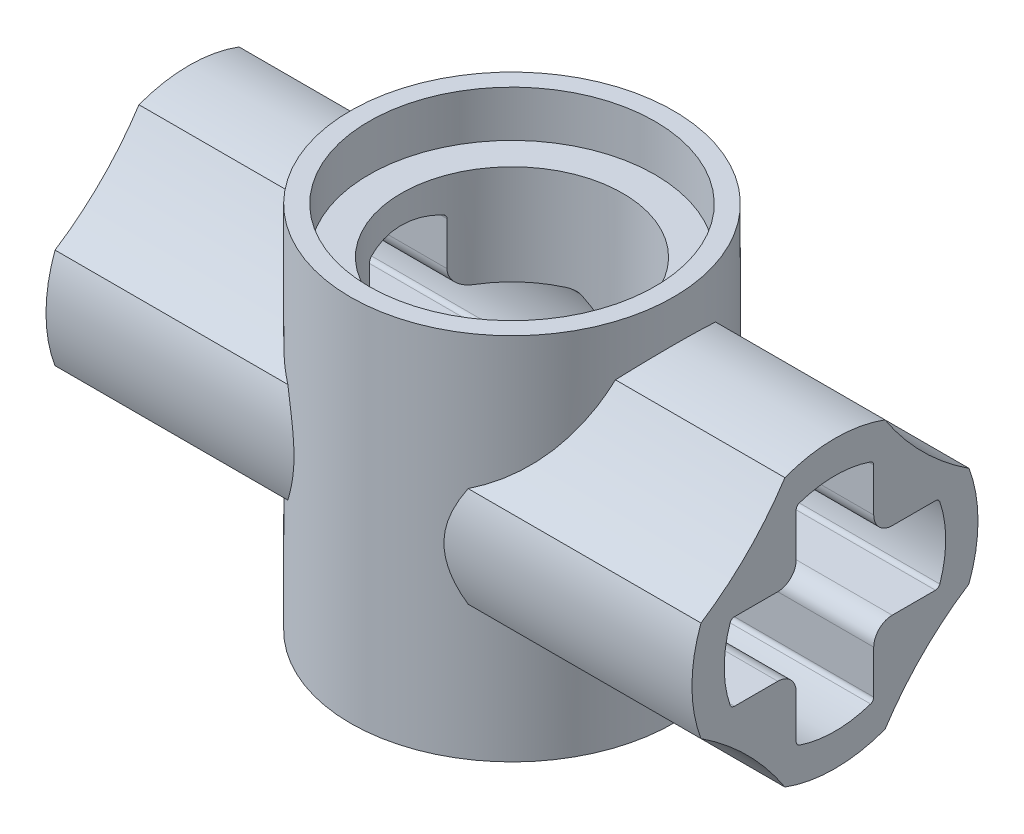
SolidWorks part; units mm, degrees
ref_plane "Front Plane" through (0, 0, 0) normal (0, 0, 1) x (1, 0, 0)
ref_plane "Top Plane" through (0, 0, 0) normal (0, 1, 0) x (1, 0, 0)
ref_plane "Right Plane" through (0, 0, 0) normal (1, 0, 0) x (0, 0, -1)
sketch "Sketch1" plane through (0, 0, 0) normal (1, 0, 0) x (0, 0, -1)
  line L0 (1.085, -1.085) -> (2.9039, -1.085)
  line L2 (-1.085, 2.9039) -> (-1.085, 1.085)
  line L4 (1.085, 2.9039) -> (1.085, 1.085)
  line L5 (-1.085, 2.9039) -> (1.085, -2.9039) construction
  line L6 (-1.085, -2.9039) -> (1.085, 2.9039) construction
  line L7 (-2.9039, 1.085) -> (-1.085, 1.085)
  line L9 (-2.9039, -1.085) -> (-1.085, -1.085)
  line L11 (-2.9039, 1.085) -> (2.9039, -1.085) construction
  line L12 (-2.9039, -1.085) -> (2.9039, 1.085) construction
  line L13 (1.085, -1.085) -> (1.085, -2.9039)
  line L14 (1.085, 1.085) -> (2.9039, 1.085)
  line L15 (-1.085, -1.085) -> (-1.085, -2.9039)
  arc A0 (1.085, 2.9039) -> (-1.085, 2.9039) centre (0, 0) ccw
  arc A1 (-2.9039, 1.085) -> (-2.9039, -1.085) centre (0, 0) ccw
  arc A2 (-1.085, -2.9039) -> (1.085, -2.9039) centre (0, 0) ccw
  arc A3 (2.9039, -1.085) -> (2.9039, 1.085) centre (0, 0) ccw
  dimension "D1" = 6.2
  dimension "D2" = 2.17
  dimension "D3" = 2.17
extrude "Boss-Extrude1" add sketch "Sketch1" against normal blind 14
fillet "Fillet1" radius 6.2 1 edges at (-7, 1.085, -1.085)
fillet "Fillet2" radius 6.2 1 edges at (-7, 1.085, 1.085)
fillet "Fillet3" radius 6.2 1 edges at (-7, -1.085, 1.085)
fillet "Fillet4" radius 6.2 1 edges at (-7, -1.085, -1.085)
sketch "Sketch3" plane through (0, 0, 0) normal (0, 1, 0) x (1, 0, 0)
  line L0 (0, 0) -> (-14, 0) construction
  circle A0 centre (-7, 0) radius 3.5
  dimension "D2" = 7
  dimension "D1" = 14
extrude "Boss-Extrude2" add sketch "Sketch3" along normal mid plane 8
sketch "Sketch2" plane through (0, 0, 0) normal (1, 0, 0) x (0, 0, -1)
  line L0 (0.84, -0.84) -> (0.84, -2.2482)
  line L2 (-0.84, 2.2482) -> (-0.84, 0.84)
  line L4 (0.84, 2.2482) -> (0.84, 0.84)
  line L5 (-0.84, 2.2482) -> (0.84, -2.2482) construction
  line L6 (-0.84, -2.2482) -> (0.84, 2.2482) construction
  line L7 (-2.2482, 0.84) -> (-0.84, 0.84)
  line L9 (-2.2482, -0.84) -> (-0.84, -0.84)
  line L11 (-2.2482, 0.84) -> (2.2482, -0.84) construction
  line L12 (-2.2482, -0.84) -> (2.2482, 0.84) construction
  line L13 (0.84, 0.84) -> (2.2482, 0.84)
  line L14 (-0.84, -0.84) -> (-0.84, -2.2482)
  line L15 (0.84, -0.84) -> (2.2482, -0.84)
  arc A0 (0.84, 2.2482) -> (-0.84, 2.2482) centre (0, 0) ccw
  arc A1 (-2.2482, 0.84) -> (-2.2482, -0.84) centre (0, 0) ccw
  arc A2 (-0.84, -2.2482) -> (0.84, -2.2482) centre (0, 0) ccw
  arc A3 (2.2482, -0.84) -> (2.2482, 0.84) centre (0, 0) ccw
  dimension "D1" = 4.8
  dimension "D2" = 1.68
  dimension "D3" = 1.68
extrude "Cut-Extrude1" cut sketch "Sketch2" against normal through all
fillet "Fillet5" radius 0.4 1 edges at (-7, 0.84, -0.84)
fillet "Fillet6" radius 0.4 1 edges at (-7, 0.84, 0.84)
fillet "Fillet7" radius 0.4 1 edges at (-7, -0.84, 0.84)
fillet "Fillet8" radius 0.4 1 edges at (-7, -0.84, -0.84)
fillet "Fillet9" radius 0.1 1 edges at (-7, -2.2482, 0.84)
fillet "Fillet10" radius 0.1 1 edges at (-7, -2.2482, -0.84)
fillet "Fillet11" radius 0.1 1 edges at (-7, 0.84, 2.2482)
fillet "Fillet12" radius 0.1 1 edges at (-7, -0.84, 2.2482)
fillet "Fillet13" radius 0.1 1 edges at (-7, 2.2482, 0.84)
fillet "Fillet14" radius 0.1 1 edges at (-7, 2.2482, -0.84)
fillet "Fillet15" radius 0.1 1 edges at (-7, 0.84, -2.2482)
fillet "Fillet16" radius 0.1 1 edges at (-7, -0.84, -2.2482)
sketch "Sketch4" plane through (0, 4, 0) normal (0, 1, 0) x (1, 0, 0)
  circle A0 centre (-7, 0) radius 2.4
  dimension "D1" = 4.8
extrude "Cut-Extrude2" cut sketch "Sketch4" against normal through all
sketch "Sketch5" plane through (0, 4, 0) normal (0, 1, 0) x (1, 0, 0)
  circle A0 centre (-7, 0) radius 3.1
  dimension "D1" = 6.2
extrude "Cut-Extrude3" cut sketch "Sketch5" against normal blind 1
mirror "Mirror1" about plane through (0, 0, 0) normal (0, 1, 0) of "Cut-Extrude3"
